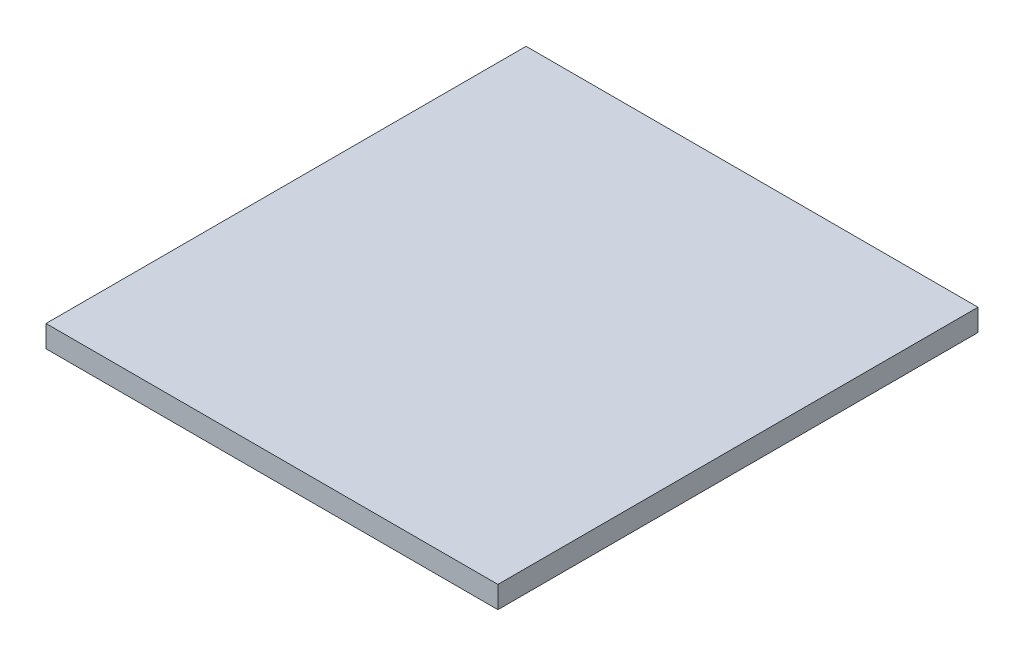
SolidWorks part; units mm, degrees
ref_plane "Front Plane" through (0, 0, 0) normal (0, 0, 1) x (1, 0, 0)
ref_plane "Top Plane" through (0, 0, 0) normal (0, 1, 0) x (1, 0, 0)
ref_plane "Right Plane" through (0, 0, 0) normal (1, 0, 0) x (0, 0, -1)
sketch "Sketch1" plane through (0, 0, 0) normal (0, 1, 0) x (1, 0, 0)
  line L1 (-54.991, -58.42) -> (54.991, -58.42)
  line L2 (-54.991, -58.42) -> (-54.991, 58.42)
  line L3 (-54.991, 58.42) -> (54.991, 58.42)
  line L4 (54.991, -58.42) -> (54.991, 58.42)
  line L5 (-54.991, -58.42) -> (54.991, 58.42) construction
  line L6 (-54.991, 58.42) -> (54.991, -58.42) construction
  point P0 (0, 0)
  dimension "D1" = 109.982
  dimension "D2" = 116.84
extrude "Boss-Extrude1" add sketch "Sketch1" along normal mid plane 5.334
equation "\"material\"=\"GMaterial@Platform.assembly\""
equation "\"D1@Boss-Extrude1\"=\"material\""
